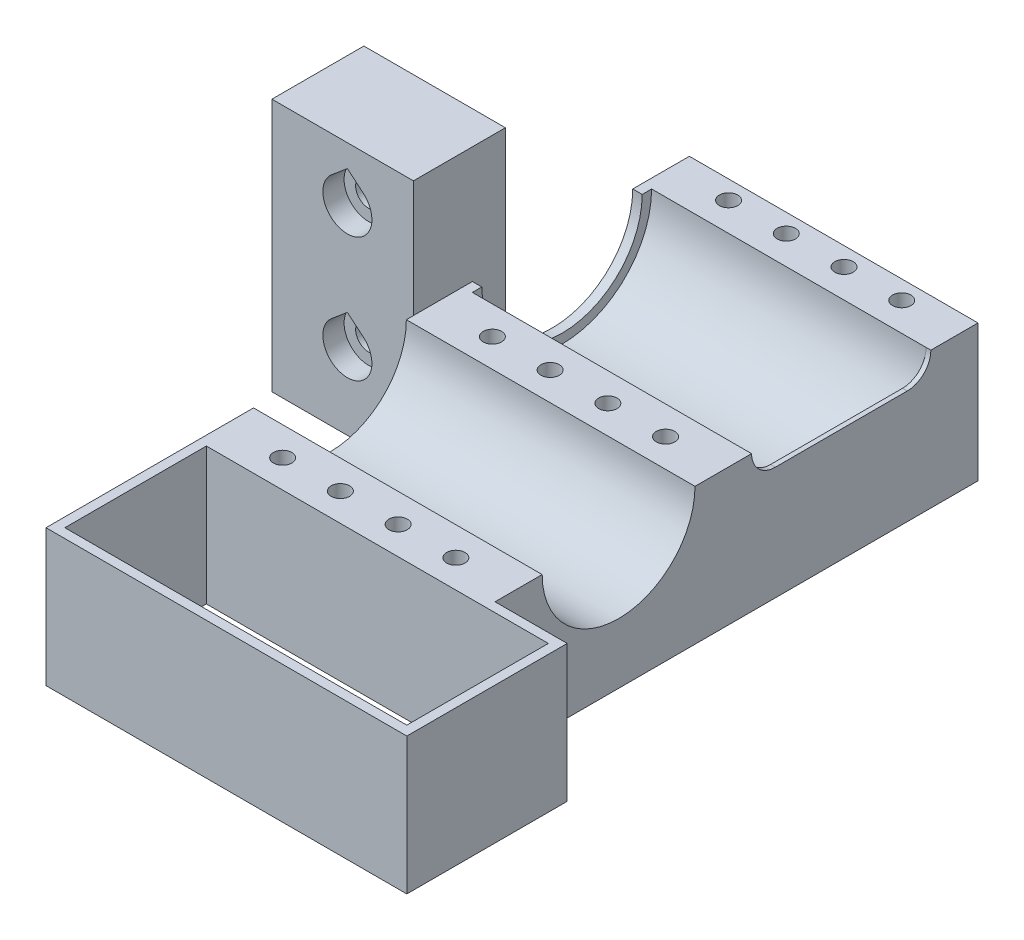
SolidWorks part; units mm, degrees
ref_plane "Front Plane" through (0, 0, 0) normal (0, 0, 1) x (1, 0, 0)
ref_plane "Top Plane" through (0, 0, 0) normal (0, 1, 0) x (1, 0, 0)
ref_plane "Right Plane" through (0, 0, 0) normal (1, 0, 0) x (0, 0, -1)
sketch "Sketch1" plane through (0, 0, 0) normal (1, 0, 0) x (0, 0, -1)
  line L0 (51.2, 42.0261) -> (51.2, 0) construction
  line L1 (0, 0) -> (102.4, 0)
  line L2 (0, 0) -> (0, 29)
  line L3 (102.4, 0) -> (102.4, 29)
  line L4 (0, 29) -> (10, 29) construction
  line L6 (42.4, 29) -> (54.4, 29) construction
  line L7 (42.4, 29) -> (54.4, 29)
  line L8 (0, 29) -> (10, 29)
  line L10 (42.4, 29) -> (54.4, 29)
  line L11 (92.4, 29) -> (102.4, 29)
  arc A0 (10, 29) -> (42.4, 29) centre (26.2, 29) ccw
  arc A1 (54.4, 29) -> (92.4, 29) centre (73.4, 29) ccw
  point P15 (73.4, 10)
  dimension "D3" = 19
  dimension "D4" = 16.2
  dimension "D1" = 10
  dimension "D2" = 12
  dimension "D5" = 10
extrude "Boss-Extrude1" add sketch "Sketch1" along normal blind 61.2 contours L8 L2 L1 L3 L7 region at (0, 11.0871, -50.0531)
sketch "Sketch7" plane through (0, 0, 0) normal (-1, 0, 0) x (0, 0, 1)
  line L0 (0, 0) -> (-102.4, 0) construction
  line L1 (-63.4, 0) -> (-43.8992, 0)
  line L2 (-63.4, 0) -> (-63.4, 53.7409)
  line L3 (-63.4, 53.7409) -> (-43.8992, 53.7409)
  line L4 (-43.8992, 0) -> (-43.8992, 53.7409)
  line L5 (-42.4, 29) -> (-54.4, 29) construction
  line L6 (-42.4, 29) -> (-54.4, 29) construction
  arc A0 (-92.4, 29) -> (-54.4, 29) centre (-73.4, 29) ccw construction
  arc A1 (-92.4, 29) -> (-54.4, 29) centre (-73.4, 29) ccw construction
  circle A2 centre (-73.4, 29) radius 6 construction
  dimension "D1" = 12
  dimension "D2" = 10
  dimension "D3" = 1.4992
extrude "Boss-Extrude2" add sketch "Sketch7" along normal blind 30
sketch "Sketch14" plane through (61.2, 0, 0) normal (1, 0, 0) x (0, 0, -1)
  line L0 (54.4, 29) -> (92.4, 29)
  arc A0 (54.4, 29) -> (92.4, 29) centre (73.4, 29) ccw construction
  arc A1 (54.4, 29) -> (92.4, 29) centre (73.4, 29) ccw
extrude "Boss-Extrude3" add sketch "Sketch14" against normal blind 1
sketch "Sketch19" plane through (0, 0, 0) normal (-1, 0, 0) x (0, 0, 1)
  line L1 (-90.4, 29) -> (-92.4, 29)
  line L2 (-56.4, 29) -> (-54.4, 29)
  arc A5 (-63.4, 12.8445) -> (-54.4, 29) centre (-73.4, 29) ccw construction
  arc A7 (-92.4, 29) -> (-63.4, 12.8445) centre (-73.4, 29) ccw construction
  arc A8 (-63.4, 12.8445) -> (-54.4, 29) centre (-73.4, 29) ccw
  arc A9 (-92.4, 29) -> (-63.4, 12.8445) centre (-73.4, 29) ccw
  arc A10 (-90.4, 29) -> (-64.4526, 14.5451) centre (-73.4, 29) ccw
  arc A11 (-64.4526, 14.5451) -> (-56.4, 29) centre (-73.4, 29) ccw
  dimension "D1" = 2
extrude "Boss-Extrude4" add sketch "Sketch19" against normal blind 2
sketch "Sketch26" plane through (0, 0, 0) normal (0, 1, 0) x (1, 0, 0)
  line L0 (2, -2) -> (74.5, -2)
  line L1 (0, 0) -> (76.5, 0)
  line L2 (0, 0) -> (0, -34)
  line L3 (0, -34) -> (76.5, -34)
  line L4 (76.5, 0) -> (76.5, -34)
  line L5 (74.5, -2) -> (74.5, -32)
  line L6 (2, -32) -> (74.5, -32)
  line L7 (2, -2) -> (2, -32)
  dimension "D1" = 34
  dimension "D2" = 76.5
  dimension "D3" = 2
extrude "Boss-Extrude5" add sketch "Sketch26" along normal blind 29
sketch "Sketch8" plane through (0, 0, -63.4) normal (0, 0, -1) x (-1, 0, 0)
  line L0 (30, 53.7409) -> (0, 53.7409) construction
  line L1 (0, 53.7409) -> (0, 15.2523) construction
  line L2 (30, 53.7409) -> (0, 53.7409) construction
  line L3 (0, 53.7409) -> (0, 15.2523) construction
  line L5 (-2, 29) -> (0, 29) construction
  line L12 (3.5, 29) -> (45.8321, 29) construction
  line L14 (-2, 29) -> (-2, 10) construction
  line L15 (-2, 29) -> (-2, 10) construction
  line L16 (-2, 29) -> (0, 29) construction
  circle A0 centre (14, 42.2) radius 2.75
  circle A1 centre (14, 15.8) radius 2.75
  point P2 (0, 0)
  dimension "D3" = 5.5
  dimension "D2" = 14
  dimension "D1" = 13.2
  dimension "D4" = 13.2
extrude "Cut-Extrude1" cut sketch "Sketch8" against normal up to surface (19.5008 mm away) up to face at (-12, 27.2964, -43.8992)
sketch "Sketch9" plane through (0, 0, -63.4) normal (0, 0, -1) x (-1, 0, 0)
  circle A0 centre (14, 42.2) radius 5.2
  circle A1 centre (14, 15.8) radius 5.2
  dimension "D1" = 10.4
extrude "Cut-Extrude2" cut sketch "Sketch9" against normal blind 4.5
sketch "Sketch10" plane through (0, 0, -43.8992) normal (0, 0, 1) x (1, 0, 0)
  circle A0 centre (-14, 42.2) radius 5.2
  circle A1 centre (-14, 15.8) radius 5.2
  dimension "D1" = 10.4
extrude "Cut-Extrude8" cut sketch "Sketch10" against normal blind 4.5
sketch "Sketch22" plane through (0, 29, 0) normal (0, 1, 0) x (1, 0, 0)
  line L0 (61.2, 42.4) -> (0, 42.4) construction
  line L1 (60.2, 54.4) -> (2, 54.4) construction
  line L2 (61.2, 42.4) -> (0, 42.4) construction
  line L3 (60.2, 54.4) -> (2, 54.4) construction
  line L4 (30.6, 54.4) -> (30.6, 42.4) construction
  line L5 (30.6, 48.4) -> (0, 48.4) construction
  line L6 (30.6, 48.4) -> (61.2, 48.4) construction
  line L7 (61.2, 42.4) -> (61.2, 102.4) construction
  line L8 (61.2, 10) -> (61.2, 42.4) construction
  line L9 (60.2, 92.4) -> (60.2, 54.4) construction
  line L10 (61.2, 10) -> (61.2, 42.4) construction
  line L11 (60.2, 92.4) -> (60.2, 54.4) construction
  line L12 (60.2, 73.4) -> (-4.6102, 73.4) construction
  line L13 (61.2, 26.2) -> (-9.4707, 26.2) construction
  line L14 (-21.9217, 98.47) -> (51.6485, 98.47) construction
  line L15 (76.5, 0) -> (61.2, 0) construction
  line L16 (10.6744, 3.93) -> (59.5979, 3.93) construction
  line L17 (0, 43.8992) -> (0, 63.4) construction
  line L18 (61.2, 102.4) -> (0, 102.4) construction
  line L19 (0, 43.8992) -> (0, 63.4) construction
  circle A0 centre (12.24, 48.4) radius 1.95
  circle A1 centre (24.48, 48.4) radius 1.95
  circle A2 centre (36.72, 48.4) radius 1.95
  circle A3 centre (48.96, 48.4) radius 1.95
  circle A5 centre (48.96, 98.47) radius 1.95
  circle A8 centre (24.48, 98.47) radius 1.95
  circle A9 centre (12.24, 98.47) radius 1.95
  circle A10 centre (36.72, 3.93) radius 1.95
  circle A11 centre (48.96, 3.93) radius 1.95
  circle A14 centre (12.24, 3.93) radius 1.95
  circle A15 centre (36.72, 98.47) radius 1.95
  circle A16 centre (24.48, 3.93) radius 1.95
  dimension "D1" = 3.9
  dimension "D7" = 3.93
  dimension "D8" = 3.93
  dimension "D2" = 12.24
  dimension "D3" = 61.2
  dimension "D4" = 12.24
  dimension "D5" = 12.24
  dimension "D6" = 12.24
extrude "Cut-Extrude9" cut sketch "Sketch22" against normal up to surface (29 mm away) up to face at (21.54, 0, -35.1398)
sketch "Sketch24" plane through (0, 0, 0) normal (0, -1, 0) x (1, 0, 0)
  line L0 (74.5, 2) -> (2, 2) construction
  line L1 (15.7041, -3.93) -> (13.9721, -0.93)
  line L2 (13.9721, -0.93) -> (10.5079, -0.93)
  line L3 (10.5079, -0.93) -> (8.7759, -3.93)
  line L4 (8.7759, -3.93) -> (10.5079, -6.93)
  line L5 (10.5079, -6.93) -> (13.9721, -6.93)
  line L6 (13.9721, -6.93) -> (15.7041, -3.93)
  line L7 (27.9441, -3.93) -> (26.2121, -0.93)
  line L8 (26.2121, -0.93) -> (22.7479, -0.93)
  line L9 (22.7479, -0.93) -> (21.0159, -3.93)
  line L10 (21.0159, -3.93) -> (22.7479, -6.93)
  line L11 (22.7479, -6.93) -> (26.2121, -6.93)
  line L12 (26.2121, -6.93) -> (27.9441, -3.93)
  line L13 (40.1841, -3.93) -> (38.4521, -0.93)
  line L14 (38.4521, -0.93) -> (34.9879, -0.93)
  line L15 (34.9879, -0.93) -> (33.2559, -3.93)
  line L16 (33.2559, -3.93) -> (34.9879, -6.93)
  line L17 (34.9879, -6.93) -> (38.4521, -6.93)
  line L18 (38.4521, -6.93) -> (40.1841, -3.93)
  line L19 (52.4241, -3.93) -> (50.6921, -0.93)
  line L20 (50.6921, -0.93) -> (47.2279, -0.93)
  line L21 (47.2279, -0.93) -> (45.4959, -3.93)
  line L22 (45.4959, -3.93) -> (47.2279, -6.93)
  line L23 (47.2279, -6.93) -> (50.6921, -6.93)
  line L24 (50.6921, -6.93) -> (52.4241, -3.93)
  line L25 (45.4959, -48.4009) -> (47.2287, -51.4005)
  line L26 (47.2287, -51.4005) -> (50.6928, -51.3995)
  line L27 (50.6928, -51.3995) -> (52.4241, -48.3991)
  line L28 (52.4241, -48.3991) -> (50.6913, -45.3995)
  line L29 (50.6913, -45.3995) -> (47.2272, -45.4005)
  line L30 (47.2272, -45.4005) -> (45.4959, -48.4009)
  line L31 (33.2559, -48.4007) -> (34.9885, -51.4003)
  line L32 (34.9885, -51.4003) -> (38.4526, -51.3997)
  line L33 (38.4526, -51.3997) -> (40.1841, -48.3993)
  line L34 (40.1841, -48.3993) -> (38.4515, -45.3997)
  line L35 (38.4515, -45.3997) -> (34.9874, -45.4003)
  line L36 (34.9874, -45.4003) -> (33.2559, -48.4007)
  line L37 (21.0159, -48.4005) -> (22.7484, -51.4003)
  line L38 (22.7484, -51.4003) -> (26.2125, -51.3997)
  line L39 (26.2125, -51.3997) -> (27.9441, -48.3995)
  line L40 (27.9441, -48.3995) -> (26.2116, -45.3997)
  line L41 (26.2116, -45.3997) -> (22.7475, -45.4003)
  line L42 (22.7475, -45.4003) -> (21.0159, -48.4005)
  line L43 (8.7759, -48.4005) -> (10.5083, -51.4002)
  line L44 (10.5083, -51.4002) -> (13.9724, -51.3998)
  line L45 (13.9724, -51.3998) -> (15.7041, -48.3995)
  line L46 (15.7041, -48.3995) -> (13.9717, -45.3998)
  line L47 (13.9717, -45.3998) -> (10.5076, -45.4002)
  line L48 (10.5076, -45.4002) -> (8.7759, -48.4005)
  line L49 (10.5079, -95.47) -> (8.7759, -98.47)
  line L50 (8.7759, -98.47) -> (10.5079, -101.47)
  line L51 (10.5079, -101.47) -> (13.9721, -101.47)
  line L52 (13.9721, -101.47) -> (15.7041, -98.47)
  line L53 (15.7041, -98.47) -> (13.9721, -95.47)
  line L54 (13.9721, -95.47) -> (10.5079, -95.47)
  line L55 (22.7479, -95.47) -> (21.0159, -98.47)
  line L56 (21.0159, -98.47) -> (22.7479, -101.47)
  line L57 (22.7479, -101.47) -> (26.2121, -101.47)
  line L58 (26.2121, -101.47) -> (27.9441, -98.47)
  line L59 (27.9441, -98.47) -> (26.2121, -95.47)
  line L60 (26.2121, -95.47) -> (22.7479, -95.47)
  line L61 (34.9879, -95.47) -> (33.2559, -98.47)
  line L62 (33.2559, -98.47) -> (34.9879, -101.47)
  line L63 (34.9879, -101.47) -> (38.4521, -101.47)
  line L64 (38.4521, -101.47) -> (40.1841, -98.47)
  line L65 (40.1841, -98.47) -> (38.4521, -95.47)
  line L66 (38.4521, -95.47) -> (34.9879, -95.47)
  line L67 (47.2279, -95.47) -> (45.4959, -98.47)
  line L68 (45.4959, -98.47) -> (47.2279, -101.47)
  line L69 (47.2279, -101.47) -> (50.6921, -101.47)
  line L70 (50.6921, -101.47) -> (52.4241, -98.47)
  line L71 (52.4241, -98.47) -> (50.6921, -95.47)
  line L72 (50.6921, -95.47) -> (47.2279, -95.47)
  line L73 (61.2, -102.4) -> (0, -102.4) construction
  circle A0 centre (12.24, -3.93) radius 3 construction
  circle A1 centre (24.48, -3.93) radius 3 construction
  circle A2 centre (36.72, -3.93) radius 3 construction
  circle A3 centre (48.96, -3.93) radius 3 construction
  circle A4 centre (48.96, -48.4) radius 3 construction
  circle A5 centre (36.72, -48.4) radius 3 construction
  circle A6 centre (24.48, -48.4) radius 3 construction
  circle A7 centre (12.24, -48.4) radius 3 construction
  circle A8 centre (12.24, -98.47) radius 3 construction
  circle A9 centre (24.48, -98.47) radius 3 construction
  circle A10 centre (36.72, -98.47) radius 3 construction
  circle A11 centre (48.96, -98.47) radius 3 construction
  dimension "D1" = 6
extrude "Cut-Extrude10" cut sketch "Sketch24" against normal blind 4.5
sketch "Sketch25" plane through (61.2, 0, 0) normal (1, 0, 0) x (0, 0, -1)
  line L0 (59.4, 29) -> (87.4, 29) construction
  line L1 (42.4, 29) -> (102.4, 29) construction
  line L2 (59.4, 34) -> (87.4, 34)
  line L3 (59.4, 24) -> (87.4, 24)
  line L6 (92.4, 29) -> (54.4, 29) construction
  line L7 (92.4, 29) -> (54.4, 29) construction
  arc A0 (59.4, 34) -> (59.4, 24) centre (59.4, 29) ccw
  arc A1 (87.4, 24) -> (87.4, 34) centre (87.4, 29) ccw
  point P5 (73.4, 29)
  point P12 (92.4, 29)
  dimension "D1" = 10
extrude "Cut-Extrue11" cut sketch "Sketch25" against normal blind 2
chamfer "Chamfer1" [suppressed] distance 1 angle 45
split "Split1" bodies to split 126 resulting bodies 128 129 split by face at (0, 35.9789, -53.8698)
sketch "Sketch27" plane through (0, 0, -63.4) normal (0, 0, -1) x (-1, 0, 0)
  line L0 (14, 48.9881) -> (10.6575, 46.1834)
  line L1 (14, 48.9881) -> (17.3425, 46.1834)
  line L2 (10.6575, 46.1834) -> (17.3425, 46.1834) construction
  line L3 (10.6575, 19.7834) -> (14, 22.5881)
  line L4 (14, 22.5881) -> (17.3425, 19.7834)
  line L5 (10.6575, 19.7834) -> (17.3425, 19.7834) construction
  circle A0 centre (14, 15.8) radius 5.2 construction
  circle A1 centre (14, 42.2) radius 5.2 construction
  arc A2 (17.3425, 19.7834) -> (10.6575, 19.7834) centre (14, 15.8) ccw
  arc A3 (17.3425, 46.1834) -> (10.6575, 46.1834) centre (14, 42.2) ccw
  circle A4 centre (14, 42.2) radius 5.2 construction
  dimension "D1" = 40
  dimension "D2" = 40
extrude "Cut-Extrude12" cut sketch "Sketch27" against normal up to surface (4.5 mm away) up to face at (-19.2, 42.2, -58.9)
sketch "Sketch28" plane through (0, 0, -43.8992) normal (0, 0, 1) x (1, 0, 0)
  line L2 (-10.6575, 46.1834) -> (-14, 48.9881)
  line L3 (-14, 48.9881) -> (-17.3425, 46.1834)
  line L4 (-10.6575, 46.1834) -> (-14, 48.9881)
  line L5 (-14, 48.9881) -> (-17.3425, 46.1834)
  line L6 (-10.6575, 19.7834) -> (-14, 22.5881)
  line L7 (-14, 22.5881) -> (-17.3425, 19.7834)
  line L8 (-10.6575, 19.7834) -> (-14, 22.5881)
  line L9 (-14, 22.5881) -> (-17.3425, 19.7834)
  arc A1 (-10.6575, 46.1834) -> (-17.3425, 46.1834) centre (-14, 42.2) ccw
  arc A2 (-10.6575, 46.1834) -> (-17.3425, 46.1834) centre (-14, 42.2) ccw
  arc A3 (-10.6575, 19.7834) -> (-17.3425, 19.7834) centre (-14, 15.8) ccw
  arc A4 (-10.6575, 19.7834) -> (-17.3425, 19.7834) centre (-14, 15.8) ccw
  dimension "D1" = 0
  dimension "D2" = 0
extrude "Cut-Extrude13" cut sketch "Sketch28" against normal up to surface (4.5 mm away) up to face at (-8.8, 42.2, -48.3992)
equation "\"MotorDIA\"= 37' Motor Diameter"
equation "\"SyringeDIA\"= 31.4'60ml Syringe Diameter"
equation "\"MotorShaftDIA\"= 6'Motor Shaft Dia"
equation "\"MotorKeyway\"= 1'Motor Shaft Keyway Depth"
equation "\"MotorLength\"= 56.7'Motor Length Excluding Shaft"
equation "\"SyringeLength\"= 117.3'60ml Syringe Length Excluding Nozzle"
equation "\"3Dtol\"= .5'Sizing Tolerance for 3D printed parts"
equation "\"ChamberDIA\"= 100 - 4'Buoyancy Chamber inner Diameter"
equation "\"ChamberThk\"= 2mm'Buoyancy Chamber Wall Thickness"
equation "\"D4@Sketch1\"=\"SyringeDIA\"/2+\"3Dtol\""
equation "\"D3@Sketch1\"=\"MotorDIA\"/2+\"3Dtol\""
equation "\"D1@Boss-Extrude1\"=\"MotorLength\"+\"3Dtol\"+4"
equation "\"D4@Sketch8\"=\"D1@Sketch8\""
equation "\"BearingOD\"= 10"
equation "\"BearingID\"= 4"
equation "\"Bearingwidth\"= 4"
equation "\"ShaftDIA\"= 4"
equation "\"D2@Sketch22\"=\"D3@Sketch22\"/5"
equation "\"D4@Sketch22\"=\"D2@Sketch22\""
equation "\"D5@Sketch22\"=\"D4@Sketch22\""
equation "\"D6@Sketch22\"=\"D5@Sketch22\""
